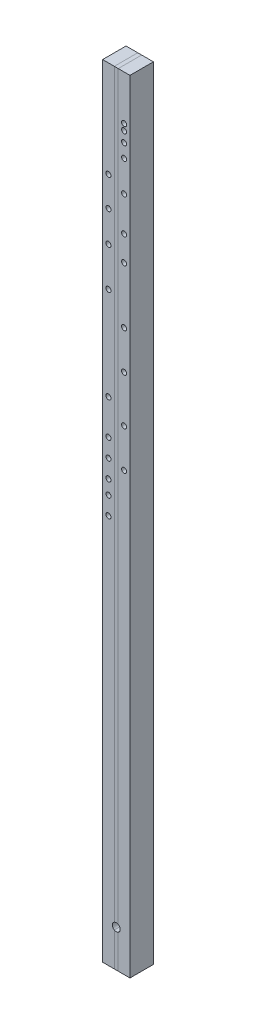
SolidWorks part; units mm, degrees
ref_plane "Front Plane" through (0, 0, 0) normal (0, 0, 1) x (1, 0, 0)
ref_plane "Top Plane" through (0, 0, 0) normal (0, 1, 0) x (1, 0, 0)
ref_plane "Right Plane" through (0, 0, 0) normal (1, 0, 0) x (0, 0, -1)
sketch "Sketch1" plane through (0, 0, 0) normal (1, 0, 0) x (0, 0, -1)
  line L1 (19.05, 635) -> (-19.05, 635)
  line L2 (19.05, 635) -> (19.05, -635)
  line L3 (19.05, -635) -> (-19.05, -635)
  line L4 (-19.05, 635) -> (-19.05, -635)
  line L5 (19.05, 635) -> (-19.05, -635) construction
  line L6 (19.05, -635) -> (-19.05, 635) construction
  point P0 (0, 0)
  dimension "D1" = 1270
  dimension "D2" = 38.1
extrude "Boss-Extrude1" add sketch "Sketch1" along normal mid plane 6.35
sketch "Sketch8" plane through (3.175, 0, 0) normal (1, 0, 0) x (0, 0, -1)
  line L4 (-19.05, 635) -> (-19.05, -635)
  line L5 (-19.05, -635) -> (19.05, -635)
  line L6 (19.05, -635) -> (19.05, 635)
  line L7 (19.05, 635) -> (-19.05, 635)
  line L8 (-19.05, 635) -> (-19.05, -635)
  line L9 (-19.05, -635) -> (19.05, -635)
  line L10 (19.05, -635) -> (19.05, 635)
  line L11 (19.05, 635) -> (-19.05, 635)
  dimension "D1" = 0
extrude "Boss-Extrude2" add sketch "Sketch8" along normal blind 19.05 separate body
mirror "Mirror3" about plane through (0, 0, 0) normal (1, 0, 0) of bodies 108
sketch "Sketch2" plane through (0, 0, 19.05) normal (0, 0, 1) x (1, 0, 0)
  line L0 (3.175, -635) -> (-3.175, -635) construction
  line L1 (0, -574.675) -> (0, -635) construction
  circle A0 centre (0, -574.675) radius 6.35
  dimension "D2" = 12.7
  dimension "D1" = 60.325
extrude "Cut-Extrude1" cut sketch "Sketch2" against normal through all
sketch "Sketch3" plane through (0, 0, 0) normal (1, 0, 0) x (0, 0, -1)
  line L0 (-50.8, -57.2492) -> (-60.325, -514.35)
  line L2 (-19.05, -635) -> (19.05, -635) construction
  line L3 (-61.8686, -234.8572) -> (-138.4329, -233.2617) construction
  line L4 (-53.684, -195.6492) -> (-68.4128, -195.3423)
  line L5 (-53.684, -195.6492) -> (-55.3244, -274.3721)
  line L6 (-55.3244, -274.3721) -> (-70.0532, -274.0652)
  line L7 (-68.4128, -195.3423) -> (-70.0532, -274.0652)
  line L8 (-53.684, -195.6492) -> (-70.0532, -274.0652) construction
  line L9 (-55.3244, -274.3721) -> (-68.4128, -195.3423) construction
  line L10 (-207.7652, -238.1684) -> (-69.3653, -241.0523)
  line L11 (-207.7652, -238.1684) -> (-207.5006, -225.4711)
  line L12 (-207.5006, -225.4711) -> (-69.1007, -228.3551)
  line L13 (-69.3653, -241.0523) -> (-69.1007, -228.3551)
  line L14 (-207.7652, -238.1684) -> (-69.1007, -228.3551) construction
  line L15 (-207.5006, -225.4711) -> (-69.3653, -241.0523) construction
  line L16 (-19.05, 635) -> (-19.05, -569.1757) construction
  circle A0 centre (-55.5625, -285.7996) radius 228.6
  point P12 (-61.8686, -234.8572)
  point P13 (-138.4329, -233.2617)
  dimension "D1" = 457.2
  dimension "D2" = 31.75
  dimension "D3" = 120.65
  dimension "D4" = 12.7
  dimension "D5" = 138.43
  dimension "D6" = 78.74
  dimension "D7" = 14.732
  dimension "D8" = 41.275
  dimension "D9" = 177.8
ref_plane "Plane1" through (0, -236.0439, 4.9186) normal (0, 0.9998, -0.0208) x (0, 0.0208, 0.9998)
sketch "Sketch7" plane through (0, -236.0439, 4.9186) normal (0, 0.9998, -0.0208) x (0, 0.0208, 0.9998)
  line L0 (202.7583, 0) -> (64.3283, 0) construction
  line L1 (217.5832, 38.1) -> (55.0735, 38.1)
  line L2 (217.5832, 38.1) -> (217.5832, -38.1)
  line L3 (217.5832, -38.1) -> (55.0735, -38.1)
  line L4 (55.0735, 38.1) -> (55.0735, -38.1)
  line L5 (217.5832, 38.1) -> (55.0735, -38.1) construction
  line L6 (217.5832, -38.1) -> (55.0735, 38.1) construction
  point P0 (136.3283, 0)
  dimension "D1" = 76.2
sketch "Sketch5" plane through (0, 0, 19.05) normal (0, 0, 1) x (1, 0, 0)
  line L0 (12.7, 635) -> (12.7, -635) construction
  line L1 (3.175, 635) -> (-3.175, 635) construction
  line L2 (3.175, -635) -> (-3.175, -635) construction
  line L3 (12.7, -635) -> (-12.7, -635) construction
  line L4 (-12.7, -635) -> (-12.7, 635) construction
  line L5 (-12.7, 635) -> (12.7, 635) construction
  line L8 (0, 0) -> (-12.7, 0) construction
  line L9 (0, 0) -> (12.7, 0) construction
  circle A0 centre (12.7, 513.3021) radius 1.905
  circle A1 centre (-12.7, 478.2636) radius 1.905
  circle A2 centre (12.7, 463.3456) radius 1.905
  circle A3 centre (-12.7, 430.1139) radius 1.905
  circle A4 centre (12.7, 407.0641) radius 1.905
  circle A5 centre (-12.7, 379.8427) radius 1.905
  circle A6 centre (12.7, 366.5515) radius 1.905
  circle A7 centre (-12.7, 316.419) radius 1.905
  circle A8 centre (12.7, 535.4221) radius 1.905
  circle A9 centre (12.7, 552.285) radius 1.905
  circle A10 centre (12.7, 562.4307) radius 1.905
  circle A11 centre (-12.7, 165.1498) radius 1.905
  circle A12 centre (-12.7, 108.4563) radius 1.905
  circle A13 centre (-12.7, 79.0585) radius 1.905
  circle A14 centre (-12.7, 49.6539) radius 1.905
  circle A15 centre (-12.7, 27.0432) radius 1.905
  circle A16 centre (-12.7, -2.1989) radius 1.905
  circle A17 centre (12.7, 74.3869) radius 1.905
  circle A18 centre (12.7, 137.0132) radius 1.905
  circle A19 centre (12.7, 212.5967) radius 1.905
  circle A20 centre (12.7, 275.1797) radius 1.905
  dimension "D3" = 3.81
  dimension "D1" = 25.4
extrude "Cut-Extrude3" cut sketch "Sketch5" against normal through all
sketch "Sketch6" plane through (0, 0, 19.05) normal (0, 0, 1) x (1, 0, 0)
  circle A0 centre (12.7, 513.3021) radius 4.1275
  circle A1 centre (-12.7, 478.2636) radius 4.1275
  circle A2 centre (12.7, 463.3456) radius 4.1275
  circle A3 centre (-12.7, 430.1139) radius 4.1275
  circle A4 centre (-12.7, 379.8427) radius 4.1275
  circle A5 centre (-12.7, 316.419) radius 4.1275
  circle A6 centre (12.7, 366.5515) radius 4.1275
  circle A7 centre (12.7, 407.0641) radius 4.1275
  circle A8 centre (12.7, 562.4307) radius 4.1275
  circle A9 centre (12.7, 552.285) radius 4.1275
  circle A10 centre (12.7, 535.4221) radius 4.1275
  circle A11 centre (12.7, 275.1797) radius 4.1275
  circle A12 centre (12.7, 212.5967) radius 4.1275
  circle A13 centre (-12.7, 165.1498) radius 4.1275
  circle A14 centre (12.7, 137.0132) radius 4.1275
  circle A15 centre (-12.7, 108.4563) radius 4.1275
  circle A16 centre (-12.7, 79.0585) radius 4.1275
  circle A17 centre (12.7, 74.3869) radius 4.1275
  circle A18 centre (-12.7, 49.6539) radius 4.1275
  circle A19 centre (-12.7, 27.0432) radius 4.1275
  circle A20 centre (-12.7, -2.1989) radius 4.1275
  dimension "D1" = 8.255
extrude "Cut-Extrude4" cut sketch "Sketch6" against normal blind 7.747
